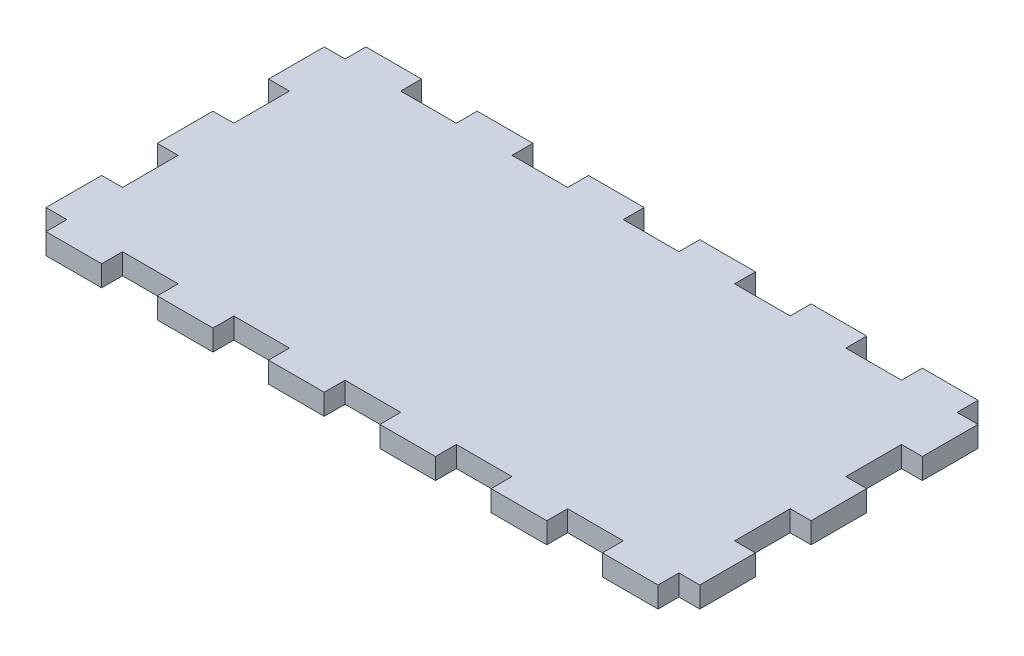
SolidWorks part; units mm, degrees
ref_plane "Front Plane" through (0, 0, 0) normal (0, 0, 1) x (1, 0, 0)
ref_plane "Top Plane" through (0, 0, 0) normal (0, 1, 0) x (1, 0, 0)
ref_plane "Right Plane" through (0, 0, 0) normal (1, 0, 0) x (0, 0, -1)
sketch "Sketch2" plane through (0, 0, 0) normal (0, 1, 0) x (1, 0, 0)
  line L1 (139.7, -63.5) -> (-139.7, -63.5)
  line L2 (139.7, -63.5) -> (139.7, 63.5)
  line L3 (139.7, 63.5) -> (-139.7, 63.5)
  line L4 (-139.7, -63.5) -> (-139.7, 63.5)
  line L5 (139.7, -63.5) -> (-139.7, 63.5) construction
  line L6 (139.7, 63.5) -> (-139.7, -63.5) construction
  point P0 (0, 0)
  dimension "D1" = 279.4
  dimension "D2" = 127
extrude "Boss-Extrude1" add sketch "Sketch2" along normal blind 9.525
sketch "Sketch3" plane through (0, 0, 63.5) normal (0, 0, 1) x (1, 0, 0)
  line L0 (-139.7, 9.525) -> (139.7, 9.525) construction
  line L1 (-139.7, 0) -> (-114.3, 0)
  line L2 (-139.7, 0) -> (-139.7, 9.525)
  line L3 (-139.7, 9.525) -> (-114.3, 9.525)
  line L4 (-114.3, 0) -> (-114.3, 9.525)
  dimension "D1" = 25.4
extrude "Boss-Extrude2" add sketch "Sketch3" along normal blind 9.525
pattern_linear "LPattern1" count 6 spacing 50.8 along (1, 0, 0) of "Boss-Extrude2"
mirror "Mirror1" about plane through (0, 0, 0) normal (0, 0, 1) of "LPattern1"
sketch "Sketch4" plane through (139.7, 0, 0) normal (1, 0, 0) x (0, 0, -1)
  line L0 (-73.025, 0) -> (73.025, 0) construction
  line L1 (-63.5, 0) -> (-38.1, 0)
  line L2 (-63.5, 0) -> (-63.5, 9.525)
  line L3 (-63.5, 9.525) -> (-38.1, 9.525)
  line L4 (-38.1, 0) -> (-38.1, 9.525)
  line L5 (-73.025, 9.525) -> (73.025, 9.525) construction
  line L6 (-73.025, 0) -> (-73.025, 9.525) construction
  dimension "D1" = 9.525
  dimension "D2" = 25.4
extrude "Boss-Extrude3" add sketch "Sketch4" along normal blind 9.525
pattern_linear "LPattern2" count 3 spacing 50.8 along (0, 0, -1) of "Boss-Extrude3"
mirror "Mirror2" about plane through (0, 0, 0) normal (1, 0, 0) of "LPattern2"
